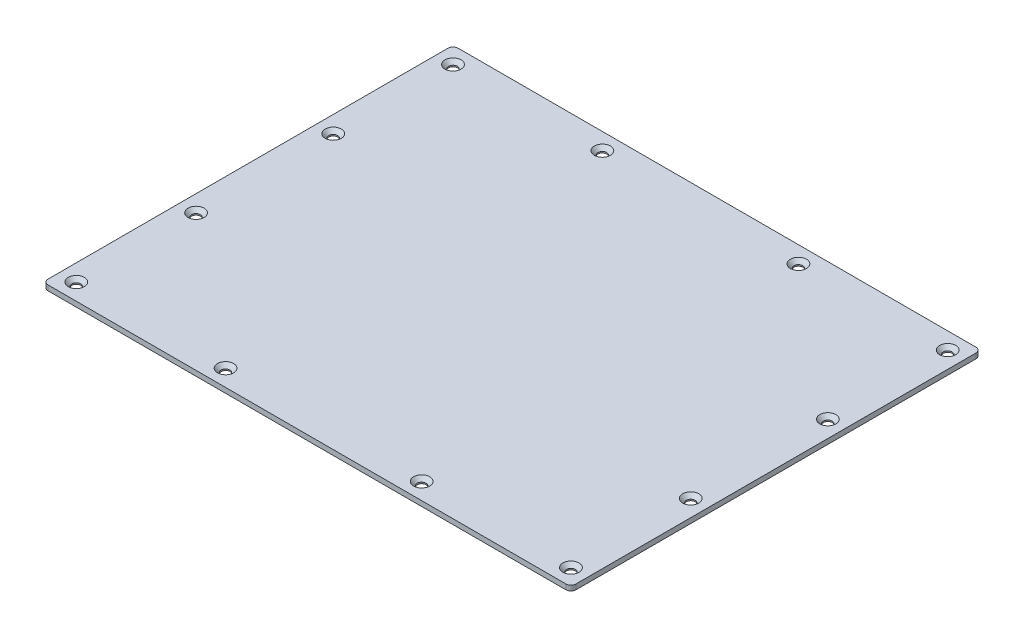
SolidWorks part; units mm, degrees
ref_plane "Front Plane" through (0, 0, 0) normal (0, 0, 1) x (1, 0, 0)
ref_plane "Top Plane" through (0, 0, 0) normal (0, 1, 0) x (1, 0, 0)
ref_plane "Right Plane" through (0, 0, 0) normal (1, 0, 0) x (0, 0, -1)
sketch "Sketch1" plane through (0, 0, 0) normal (0, 1, 0) x (1, 0, 0)
  line L0 (-103, 78) -> (-103, -78) construction
  line L1 (-101, -80) -> (101, -80) construction
  line L2 (103, -78) -> (103, 78) construction
  line L4 (101, 80) -> (-101, 80) construction
  line L31 (103, -78) -> (103, 78)
  line L32 (-101, -80) -> (101, -80)
  line L33 (101, 80) -> (-101, 80)
  line L34 (-103, 78) -> (-103, -78)
  arc A0 (-101, 80) -> (-103, 78) centre (-101, 78) ccw construction
  arc A1 (103, 78) -> (101, 80) centre (101, 78) ccw construction
  arc A2 (101, -80) -> (103, -78) centre (101, -78) ccw construction
  arc A3 (-103, -78) -> (-101, -80) centre (-101, -78) ccw construction
  arc A29 (103, 78) -> (101, 80) centre (101, 78) ccw
  arc A30 (101, -80) -> (103, -78) centre (101, -78) ccw
  arc A31 (-103, -78) -> (-101, -80) centre (-101, -78) ccw
  arc A32 (-101, 80) -> (-103, 78) centre (-101, 78) ccw
  point P6 (0, 0)
  point P32 (0, 0)
extrude "Boss-Extrude1" add sketch "Sketch1" along normal blind 2
ref_axis "Axis1" through (0, 2.1, 0) along (0, -1, 0)
sketch "Sketch2" plane through (0, 2, 0) normal (0, 1, 0) x (1, 0, 0)
  circle A0 centre (-38.25, 73.5) radius 1.4 construction
  circle A1 centre (38.25, 73.5) radius 1.4 construction
  circle A2 centre (96.5, 26.75) radius 1.4 construction
  circle A3 centre (38.25, -73.5) radius 1.4 construction
  circle A12 centre (-38.25, -73.5) radius 1.4 construction
  circle A13 centre (-96.5, -26.75) radius 1.4 construction
  circle A14 centre (-96.5, 26.75) radius 1.4 construction
  circle A15 centre (-38.25, 73.5) radius 1.4
  circle A16 centre (38.25, 73.5) radius 1.4
  circle A17 centre (96.5, 26.75) radius 1.4
  circle A18 centre (38.25, -73.5) radius 1.4
  circle A19 centre (-38.25, -73.5) radius 1.4
  circle A20 centre (-96.5, -26.75) radius 1.4
  circle A21 centre (-96.5, 26.75) radius 1.4
  circle A22 centre (-96.5, -73.5) radius 1.4 construction
  circle A23 centre (96.5, -73.5) radius 1.4 construction
  circle A24 centre (96.5, 73.5) radius 1.4 construction
  circle A25 centre (-96.5, 73.5) radius 1.4 construction
  circle A26 centre (-96.5, -73.5) radius 1.4
  circle A27 centre (96.5, -73.5) radius 1.4
  circle A28 centre (96.5, 73.5) radius 1.4
  circle A29 centre (-96.5, 73.5) radius 1.4
  circle A30 centre (96.5, -26.75) radius 1.4 construction
  circle A31 centre (96.5, -26.75) radius 1.4
  point P48 (0, 0)
hole_wizard "CSK for M3 Flat Head Machine Screw1" positions "3DSketch1" profile "Sketch3" countersink size "M3" standard "ANSI Metric" end condition through all
sketch3d "3DSketch1"
  point P0 (-96.5, 2, -73.5)
  point P3 (-96.5, 2, -26.75)
  point P6 (-38.25, 2, -73.5)
  point P9 (38.25, 2, -73.5)
  point P12 (96.5, 2, -73.5)
  point P15 (96.5, 2, -26.75)
  point P18 (96.5, 2, 26.75)
  point P21 (96.5, 2, 73.5)
  point P24 (38.25, 2, 73.5)
  point P27 (-38.25, 2, 73.5)
  point P30 (-96.5, 2, 73.5)
  point P33 (-96.5, 2, 26.75)
sketch "Sketch3" plane through (-96.5, 2, -73.5) normal (1, 0, 0) x (0, 0, 1)
  line L0 (0, 0) -> (0, 2)
  line L1 (0, 2) -> (1.725, 2)
  line L2 (1.7, 1.975) -> (1.7, 1.45)
  line L3 (1.7, 1.45) -> (3.15, 0)
  line L5 (3.15, 0) -> (0, 0)
  line L6 (-1.7, 1.45) -> (-3.15, 0) construction
  line L7 (1.725, 2) -> (1.7, 1.975)
  line L8 (-1.725, 2) -> (-1.7, 1.975) construction
  line L11 (0, -6.35) -> (0, 107.95) construction
  dimension "Thru Hole Dia." = 3.4
  dimension "Thru Hole Depth" = 2
  dimension "Near C'Sink Dia." = 6.3
  dimension "Near C'Sink Angle" = 90
  dimension "Far C'Sink Dia." = 3.45
  dimension "Far C'Sink Angle" = 90
sketch "Sketch4" plane through (0, 0, 0) normal (0, -1, 0) x (1, 0, 0)
  line L4 (103, -78) -> (103, 78)
  line L5 (101, 80) -> (-101, 80)
  line L6 (-103, 78) -> (-103, -78)
  line L7 (-101, -80) -> (101, -80)
  line L8 (103, -78) -> (103, 78)
  line L9 (101, 80) -> (-101, 80)
  line L10 (-103, 78) -> (-103, -78)
  line L11 (-101, -80) -> (101, -80)
  line L16 (102.2, -78) -> (102.2, 78)
  line L17 (101, 79.2) -> (-101, 79.2)
  line L18 (-102.2, 78) -> (-102.2, -78)
  line L19 (-101, -79.2) -> (101, -79.2)
  line L20 (102.2, -78) -> (102.2, 78)
  line L21 (101, 79.2) -> (-101, 79.2)
  line L22 (-102.2, 78) -> (-102.2, -78)
  line L23 (-101, -79.2) -> (101, -79.2)
  arc A4 (101, -80) -> (103, -78) centre (101, -78) ccw
  arc A5 (103, 78) -> (101, 80) centre (101, 78) ccw
  arc A6 (-101, 80) -> (-103, 78) centre (-101, 78) ccw
  arc A7 (-103, -78) -> (-101, -80) centre (-101, -78) ccw
  arc A8 (101, -80) -> (103, -78) centre (101, -78) ccw
  arc A9 (103, 78) -> (101, 80) centre (101, 78) ccw
  arc A10 (-101, 80) -> (-103, 78) centre (-101, 78) ccw
  arc A11 (-103, -78) -> (-101, -80) centre (-101, -78) ccw
  arc A16 (101, -79.2) -> (102.2, -78) centre (101, -78) ccw
  arc A17 (102.2, 78) -> (101, 79.2) centre (101, 78) ccw
  arc A18 (-101, 79.2) -> (-102.2, 78) centre (-101, 78) ccw
  arc A19 (-102.2, -78) -> (-101, -79.2) centre (-101, -78) ccw
  arc A20 (101, -79.2) -> (102.2, -78) centre (101, -78) ccw
  arc A21 (102.2, 78) -> (101, 79.2) centre (101, 78) ccw
  arc A22 (-101, 79.2) -> (-102.2, 78) centre (-101, 78) ccw
  arc A23 (-102.2, -78) -> (-101, -79.2) centre (-101, -78) ccw
  dimension "D1" = 0
  dimension "D2" = 0.8
